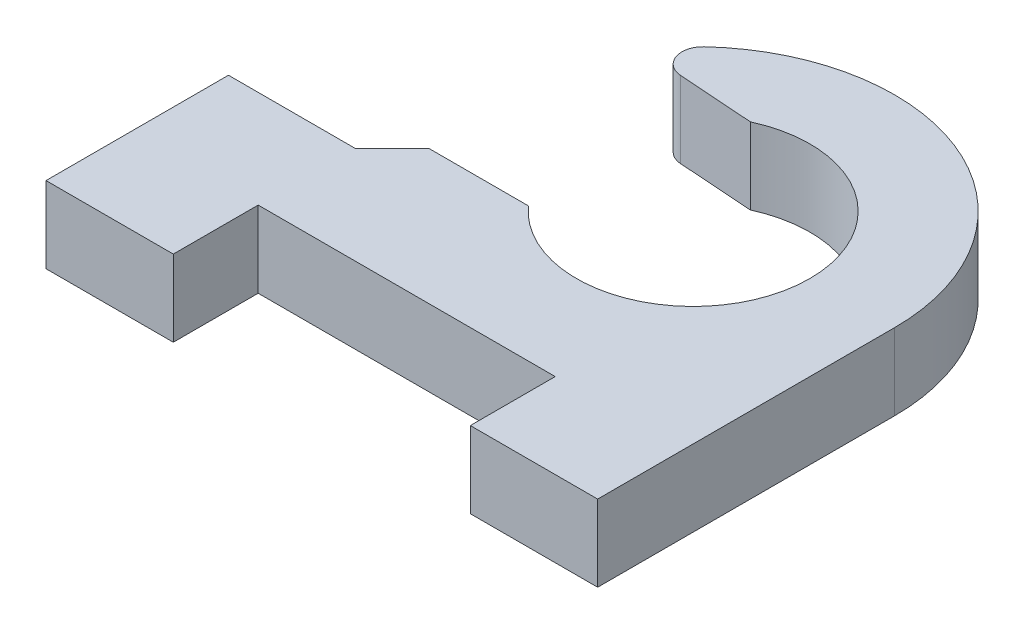
SolidWorks part; units mm, degrees
ref_plane "Front Plane" through (0, 0, 0) normal (0, 0, 1) x (1, 0, 0)
ref_plane "Top Plane" through (0, 0, 0) normal (0, 1, 0) x (1, 0, 0)
ref_plane "Right Plane" through (0, 0, 0) normal (1, 0, 0) x (0, 0, -1)
sketch "Sketch1" plane through (0, 0, 0) normal (0, 1, 0) x (1, 0, 0)
  line L0 (4.75, 0) -> (4.75, -5)
  line L1 (1.75, -5) -> (-5.25, -5)
  line L2 (-8.25, -5) -> (-8.25, -2.7)
  line L3 (-8.25, -2.7) -> (-5.25, -2.7)
  line L4 (-5.25, -2.7) -> (-4.3824, -1.8324)
  line L7 (4.75, -5) -> (4.75, -7)
  line L8 (4.75, -7) -> (1.75, -7)
  line L9 (1.75, -5) -> (1.75, -7)
  line L11 (-8.25, -5) -> (-8.25, -7)
  line L12 (-8.25, -7) -> (-5.25, -7)
  line L13 (-5.25, -5) -> (-5.25, -7)
  circle A0 centre (0, 0) radius 2.75
  arc A1 (4.75, 0) -> (-4.3824, -1.8324) centre (0, 0) ccw
  dimension "D1" = 5.5
  dimension "D2" = 9.5
  dimension "D3" = 13
  dimension "D4" = 2.3
  dimension "D5" = 5
  dimension "D6" = 225
  dimension "D7" = 3
  dimension "D8" = 2
  dimension "D9" = 3
extrude "Boss-Extrude1" add sketch "Sketch1" along normal blind 1.8
ref_axis "Axis1" through (0, 9.552, 0) along (0, -1, 0)
ref_plane "Plane1" through (0, 1.8, 0) normal (0, 1, 0) x (1, 0, 0)
sketch "Sketch2" plane through (0, 1.8, 0) normal (0, 1, 0) x (1, 0, 0)
  line L1 (-5, 2.7676) -> (0, 2.418)
  line L2 (-5, 2.7676) -> (-5, -1.8324)
  line L3 (-5, -1.8324) -> (0, -1.8324)
  line L4 (0, 2.418) -> (0, -1.8324)
  dimension "D1" = 4.6
  dimension "D2" = 0
  dimension "D3" = 5
  dimension "D4" = 0
  dimension "D5" = 94
extrude "Cut-Extrude1" cut sketch "Sketch2" against normal blind 1.8
fillet "Fillet1" radius 0.5 1 edges at (-3.9137, 0.9, -2.6917)
